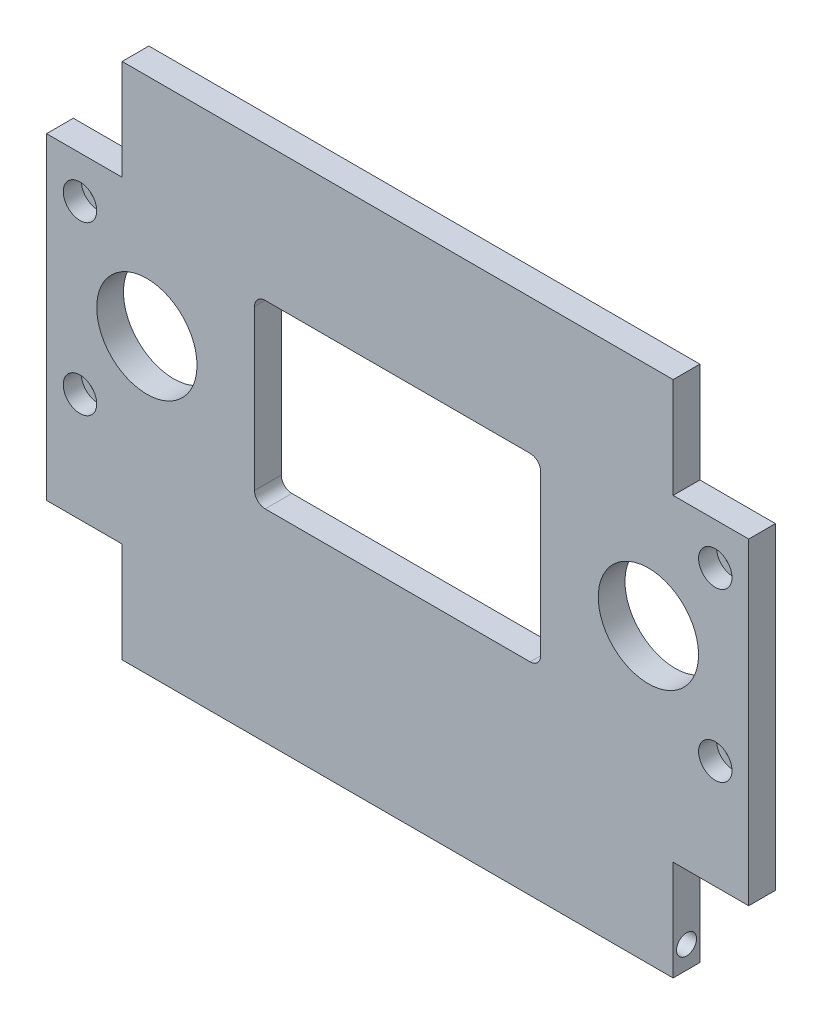
SolidWorks part; units mm, degrees
ref_plane "前视基准面" through (0, 0, 0) normal (0, 0, 1) x (1, 0, 0)
ref_plane "上视基准面" through (0, 0, 0) normal (0, 1, 0) x (1, 0, 0)
ref_plane "右视基准面" through (0, 0, 0) normal (1, 0, 0) x (0, 0, -1)
sketch "草图1" plane through (0, 0, 0) normal (0, 0, 1) x (1, 0, 0)
  line L1 (0, 0) -> (210, 0)
  line L2 (0, 0) -> (0, 75)
  line L3 (0, 75) -> (210, 75)
  line L4 (210, 0) -> (210, 75)
  dimension "D1" = 210
  dimension "D2" = 75
extrude "凸台-拉伸1" add sketch "草图1" along normal blind 8
sketch "草图2" plane through (0, 0, 8) normal (0, 0, 1) x (1, 0, 0)
  line L0 (210, 37.5) -> (0, 37.5) construction
  line L1 (210, 0) -> (210, 75) construction
  line L2 (0, 75) -> (0, 0) construction
  line L3 (0, 37.5) -> (105, 37.5) construction
  line L4 (105, 37.5) -> (105, -2.643) construction
  line L6 (144.62, 64.5) -> (65.38, 64.5)
  line L7 (147.8, 61.32) -> (147.8, 13.68)
  line L8 (144.62, 10.5) -> (65.38, 10.5)
  line L9 (62.2, 61.32) -> (62.2, 13.68)
  arc A0 (65.38, 10.5) -> (62.2, 13.68) centre (65.38, 13.68) cw
  arc A1 (62.2, 61.32) -> (65.38, 64.5) centre (65.38, 61.32) cw
  arc A2 (144.62, 10.5) -> (147.8, 13.68) centre (144.62, 13.68) ccw
  arc A3 (144.62, 64.5) -> (147.8, 61.32) centre (144.62, 61.32) cw
  point P16 (62.2, 64.5)
  point P19 (147.8, 10.5)
  point P22 (147.8, 64.5)
  dimension "D3" = 3.18
  dimension "D1" = 54
  dimension "D2" = 85.6
extrude "切除-拉伸1" cut sketch "草图2" against normal through all
hole_wizard "M5 六角凹头螺钉的柱形沉头孔1" positions "草图3" profile "草图4" counterbore size "M5" standard "ISO"
sketch "草图3" plane through (0, 0, 8) normal (0, 0, 1) x (1, 0, 0)
  line L0 (0, 37.5) -> (210, 37.5) construction
  line L1 (0, 75) -> (0, 0) construction
  line L2 (210, 0) -> (210, 75) construction
  line L3 (210, 37.5) -> (105, 37.5) construction
  line L4 (105, 37.5) -> (105, -47.7536) construction
  point P0 (10, 62.5)
  point P4 (10, 12.5)
  point P18 (200, 62.5)
  point P19 (200, 12.5)
  dimension "D1" = 50
  dimension "D2" = 10
sketch "草图4" plane through (10, 62.5, 8) normal (1, 0, 0) x (0, -1, 0)
  line L0 (0, 0) -> (0, 11.7524)
  line L1 (0, 11.7524) -> (2.75, 10.1)
  line L2 (2.75, 10.1) -> (2.75, 5.4)
  line L3 (2.75, 5.4) -> (5, 5.4)
  line L4 (5, 5.4) -> (5, 0)
  line L5 (5, 0) -> (0, 0)
  line L10 (0, 11.7524) -> (-2.75, 10.1) construction
  line L11 (0, -6.35) -> (0, 107.95) construction
  dimension "孔直径" = 5.5
  dimension "孔深度" = 10.1
  dimension "柱形沉头孔直径" = 10
  dimension "柱形沉头孔深度" = 5.4
  dimension "导头角度" = 118
sketch "草图5" plane through (0, 0, 8) normal (0, 0, 1) x (1, 0, 0)
  line L0 (0, 37.5) -> (210, 37.5) construction
  line L1 (0, 75) -> (0, 0) construction
  line L2 (210, 0) -> (210, 75) construction
  line L3 (210, 37.5) -> (105, 37.5) construction
  line L4 (105, 37.5) -> (105, 124.5038) construction
  circle A0 centre (30, 37.5) radius 15
  circle A1 centre (180, 37.5) radius 15
  dimension "D1" = 30
  dimension "D2" = 30
extrude "切除-拉伸2" cut sketch "草图5" against normal blind 13
sketch "草图6" plane through (0, 0, 0) normal (0, -1, 0) x (1, 0, 0)
  line L1 (0, 8) -> (210, 8)
  line L2 (0, 8) -> (0, 0)
  line L3 (0, 0) -> (210, 0)
  line L4 (210, 8) -> (210, 0)
extrude "凸台-拉伸2" add sketch "草图6" along normal blind 50
sketch "草图7" plane through (0, 0, 8) normal (0, 0, 1) x (1, 0, 0)
  line L0 (105, -50) -> (105, 47.0647) construction
  line L1 (0, -50) -> (22.6, -50)
  line L2 (0, -50) -> (0, -20)
  line L3 (0, -20) -> (22.6, -20)
  line L4 (22.6, -50) -> (22.6, -20)
  line L5 (210, -50) -> (0, -50) construction
  line L6 (210, -50) -> (210, -20)
  line L7 (210, -50) -> (187.4, -50)
  line L8 (187.4, -50) -> (187.4, -20)
  line L9 (210, -20) -> (187.4, -20)
  dimension "D1" = 30
  dimension "D2" = 22.6
extrude "切除-拉伸3" cut sketch "草图7" against normal blind 20
sketch "草图9" plane through (22.6, 0, 0) normal (-1, 0, 0) x (0, 0, 1)
  circle A0 centre (3.996, -43.2919) radius 3
  dimension "D1" = 6
extrude "切除-拉伸5" cut sketch "草图9" against normal blind 8
ref_plane "基准面1" through (105, 0, 0) normal (-1, 0, 0) x (0, 0, 1)
mirror "镜向1" about plane through (105, 0, 0) normal (-1, 0, 0) of "切除-拉伸5"
ref_plane "基准面2" through (0, 27.5, 0) normal (0, 1, 0) x (1, 0, 0)
sketch "草图12" plane through (0, 75, 0) normal (0, 1, 0) x (1, 0, 0)
  line L0 (105, -8) -> (105, 0) construction
  line L1 (210, -8) -> (0, -8) construction
  line L2 (210, 0) -> (0, 0) construction
  line L4 (187.4, -8) -> (22.6, -8)
  line L5 (187.4, -8) -> (187.4, 0)
  line L6 (187.4, 0) -> (22.6, 0)
  line L7 (22.6, -8) -> (22.6, 0)
  dimension "D1" = 164.8
extrude "凸台-拉伸3" add sketch "草图12" along normal blind 30
